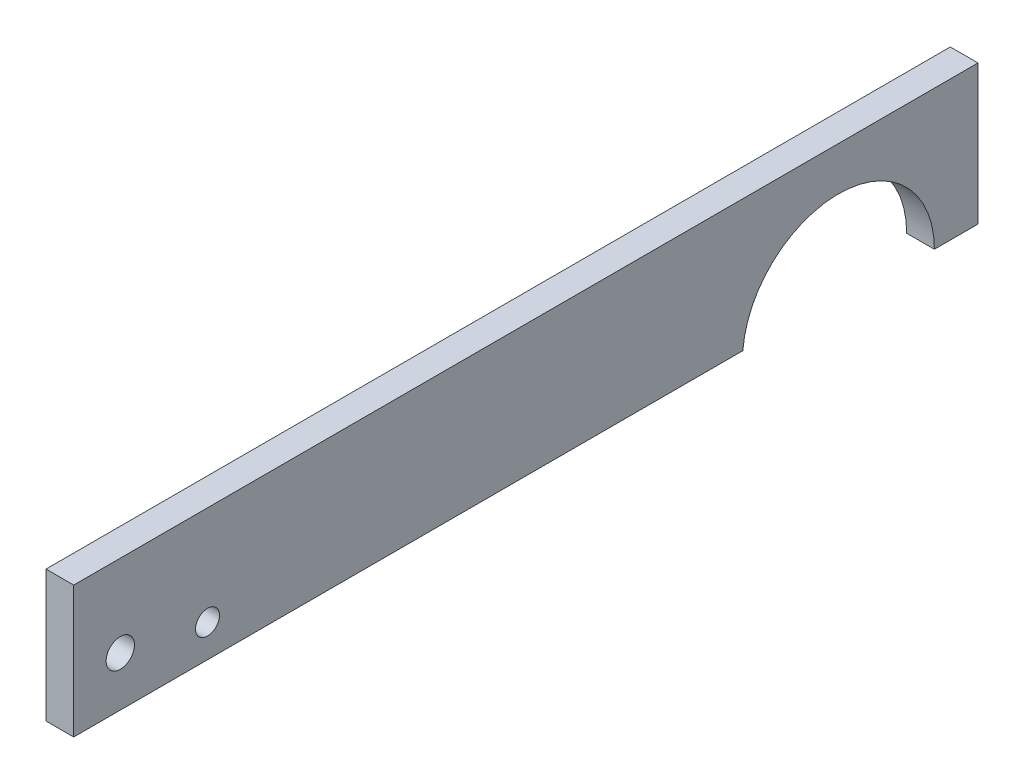
SolidWorks part; units mm, degrees
ref_plane "Front Plane" through (0, 0, 0) normal (0, 0, 1) x (1, 0, 0)
ref_plane "Top Plane" through (0, 0, 0) normal (0, 1, 0) x (1, 0, 0)
ref_plane "Right Plane" through (0, 0, 0) normal (1, 0, 0) x (0, 0, -1)
sketch "Sketch1" plane through (0, 0, 0) normal (1, 0, 0) x (0, 0, -1)
  line L0 (-175.3536, 32) -> (32, 32)
  line L1 (32, 32) -> (32, 0)
  line L2 (32, 0) -> (22, 0)
  line L9 (-175.3536, 1.8193) -> (-21.9246, 1.8193)
  line L10 (-175.3536, 32) -> (-175.3536, 1.8193)
  arc A0 (-21.9246, 1.8193) -> (22, 0) centre (0, 0) cw
  circle A1 centre (-164.67, 13.1797) radius 3.25
  circle A2 centre (-144.67, 9.2871) radius 2.75
  point P2 (-124.7114, 9.2871)
  dimension "D1" = 6.5
  dimension "D6" = 22
  dimension "D2" = 32
  dimension "D4" = 5.5
  dimension "D3" = 196.67
  dimension "D5" = 10
  dimension "D7" = 20
extrude "Boss-Extrude1" add sketch "Sketch1" along normal blind 6.35
